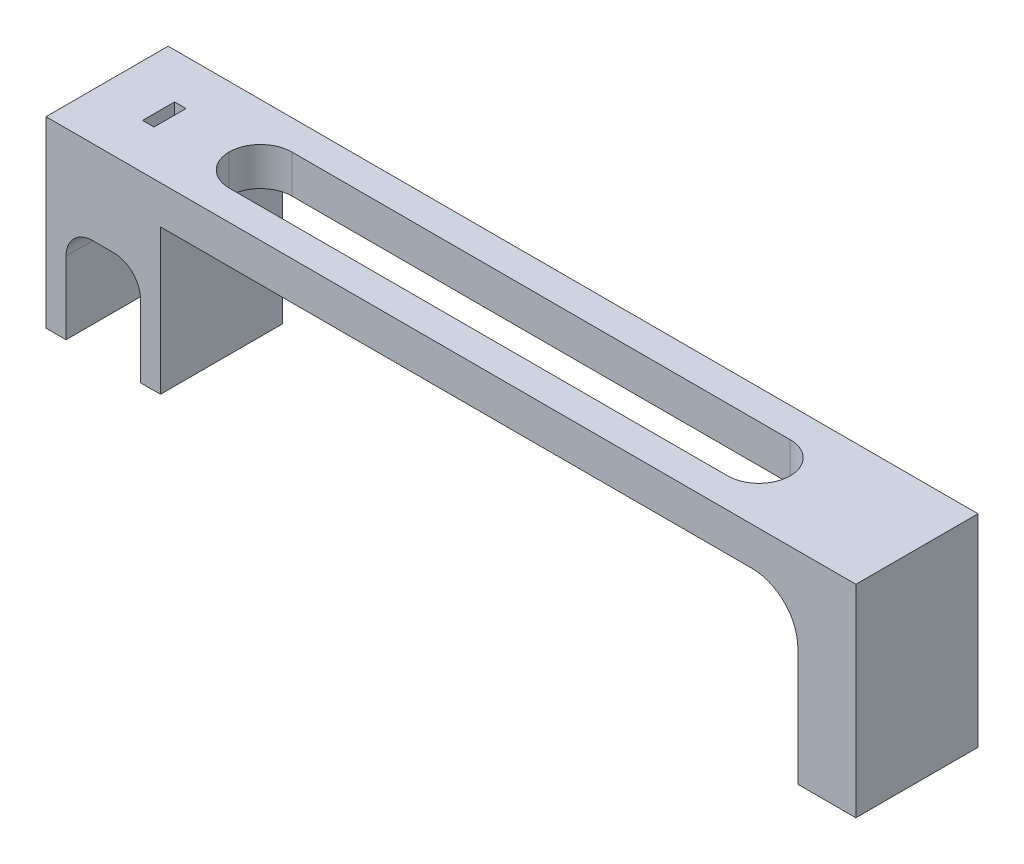
SolidWorks part; units mm, degrees
ref_plane "정면" through (0, 0, 0) normal (0, 0, 1) x (1, 0, 0)
ref_plane "윗면" through (0, 0, 0) normal (0, 1, 0) x (1, 0, 0)
ref_plane "우측면" through (0, 0, 0) normal (1, 0, 0) x (0, 0, -1)
sketch "스케치1" plane through (0, 0, 0) normal (0, 0, 1) x (1, 0, 0)
  line L0 (-96, 0) -> (0, 0)
  line L1 (0, 0) -> (0, -21.5)
  line L2 (0, -21.5) -> (7.6, -21.5)
  line L3 (7.6, -21.5) -> (7.6, 5)
  line L4 (7.6, 5) -> (-96, 5)
  line L5 (-96, 5) -> (-96, 0)
  dimension "D1" = 5
  dimension "D2" = 96
  dimension "D3" = 7.6
  dimension "D4" = 21.5
extrude "보스-돌출1" add sketch "스케치1" along normal blind 16
sketch "스케치4" plane through (0, 0, 0) normal (0, -1, 0) x (1, 0, 0)
  line L0 (-96, 8) -> (-7.1358, 8) construction
  line L1 (-96, 16) -> (-96, 0) construction
  line L2 (0, 16) -> (0, 0) construction
  line L3 (-91.75, 5.9) -> (-90.25, 5.9)
  line L4 (-91.75, 5.9) -> (-91.75, 10.1)
  line L5 (-91.75, 10.1) -> (-90.25, 10.1)
  line L6 (-90.25, 5.9) -> (-90.25, 10.1)
  line L7 (-91.75, 5.9) -> (-90.25, 10.1) construction
  line L8 (-91.75, 10.1) -> (-90.25, 5.9) construction
  line L9 (-9, 3.9) -> (-82.5, 3.9)
  line L10 (-9, 3.9) -> (-9, 12.1)
  line L11 (-9, 12.1) -> (-82.5, 12.1)
  line L12 (-82.5, 3.9) -> (-82.5, 12.1)
  line L13 (-9, 3.9) -> (-82.5, 12.1) construction
  line L14 (-9, 12.1) -> (-82.5, 3.9) construction
  point P4 (-91, 8)
  point P9 (-45.75, 8)
  dimension "D1" = 1.5
  dimension "D2" = 4.25
  dimension "D3" = 7.75
  dimension "D4" = 9
  dimension "D5" = 8.2
  dimension "D6" = 4.2
extrude "컷-돌출1" cut sketch "스케치4" against normal blind 10
fillet "필렛1" radius 4.1 4 edges at (-82.5, 2.5, 3.9) (-82.5, 2.5, 12.1) (-9, 2.5, 3.9) (-9, 2.5, 12.1)
sketch "스케치6" plane through (0, 5, 0) normal (0, 1, 0) x (1, 0, 0)
  line L0 (7.6, -16) -> (-96, -16) construction
  line L1 (-96, 0) -> (-86, 0)
  line L2 (-96, 0) -> (-96, -16)
  line L3 (-96, -16) -> (-86, -16)
  line L4 (-86, 0) -> (-86, -16)
  line L6 (-90.25, -5.9) -> (-90.25, -10.1) construction
  line M5 (-91.75, -5.9) -> (-90.25, -5.9)
  line M6 (-90.25, -5.9) -> (-90.25, -10.1)
  line M7 (-90.25, -10.1) -> (-91.75, -10.1)
  line M8 (-91.75, -10.1) -> (-91.75, -5.9)
  line M15 (7.6, 0) -> (-96, 0)
  line M16 (-96, 0) -> (-96, -16)
  line M17 (-96, -16) -> (7.6, -16)
  dimension "D1" = 4.25
extrude "보스-돌출4" add sketch "스케치6" against normal blind 11 contours L4 M15 M16 M17 M8 M5 M6 M7 region at (-91, 5, 0.1887)
sketch "스케치7" plane through (0, -21.5, 0) normal (0, -1, 0) x (1, 0, 0)
  line L0 (3.8, 16) -> (3.8, 0) construction
  line L1 (0, 16) -> (7.6, 16) construction
  line L2 (0, 0) -> (7.6, 0) construction
  line L3 (0, 8) -> (7.6, 8) construction
  line L4 (0, 16) -> (0, 0) construction
  line L5 (7.6, 16) -> (7.6, 0) construction
  line L7 (0, 16) -> (7.6, 16)
  line L8 (0, 16) -> (0, 0)
  line L9 (0, 0) -> (7.6, 0)
  line L10 (7.6, 16) -> (7.6, 0)
  line L11 (7.6, 11.75) -> (0, 11.75)
  line L12 (7.6, 11.75) -> (7.6, 4.25)
  line L13 (7.6, 4.25) -> (0, 4.25)
  line L14 (0, 11.75) -> (0, 4.25)
  line L15 (7.6, 11.75) -> (0, 4.25) construction
  line L16 (7.6, 4.25) -> (0, 11.75) construction
  line L17 (7.6, 16) -> (0, 16)
  line L18 (7.6, 16) -> (7.6, 0)
  line L19 (7.6, 0) -> (0, 0)
  line L20 (0, 16) -> (0, 0)
  line L21 (7.6, 16) -> (0, 0) construction
  line L22 (7.6, 0) -> (0, 16) construction
  point P12 (3.8, 8)
  point P23 (3.8, 8)
  dimension "D1" = 7.5
sketch "스케치10" plane through (0, -6, 0) normal (0, -1, 0) x (1, 0, 0)
  line L0 (-91, 10.1) -> (-91, 5.9) construction
  line L1 (-90.25, 10.1) -> (-91.75, 10.1) construction
  line L2 (-91.75, 5.9) -> (-90.25, 5.9) construction
  line L3 (-91.75, 8) -> (-90.25, 8) construction
  line L4 (-91.75, 10.1) -> (-91.75, 5.9) construction
  line L5 (-90.25, 5.9) -> (-90.25, 10.1) construction
  line L7 (-95.875, 0) -> (-86.125, 0)
  line L8 (-95.875, 0) -> (-95.875, 16)
  line L9 (-95.875, 16) -> (-86.125, 16)
  line L10 (-86.125, 0) -> (-86.125, 16)
  line L11 (-95.875, 0) -> (-86.125, 16) construction
  line L12 (-95.875, 16) -> (-86.125, 0) construction
  line L13 (-98.5, 0) -> (-83.5, 0)
  line L14 (-98.5, 0) -> (-98.5, 16)
  line L15 (-98.5, 16) -> (-83.5, 16)
  line L16 (-83.5, 0) -> (-83.5, 16)
  line L17 (-98.5, 0) -> (-83.5, 16) construction
  line L18 (-98.5, 16) -> (-83.5, 0) construction
  point P12 (-91, 8)
  point P17 (-91, 8)
  line M6 (-86, 0) -> (-86, 16)
  line M7 (-86, 16) -> (-96, 16)
  line M8 (-96, 16) -> (-96, 0)
  line M9 (-96, 0) -> (-86, 0)
  dimension "D1" = 9.75
  dimension "D2" = 15
extrude "보스-돌출6" add sketch "스케치10" along normal blind 13 and the other way up to vertex (11 mm away) contours L8 M9 M7 M8 | L15 L14 L13 M8 | L10 M9 M6 M7 | L13 L16 L15 M6 region at (-95.9375, -6, 8) region at (-86.0625, -6, 8) region at (-97.25, -6, 8) region at (-84.75, -6, 8) other way up to point (7.6, 5, 16)
fillet "필렛2" radius 3.5 2 edges at (-86.125, -6, 8) (-95.875, -6, 8)
fillet "필렛3" radius 6 1 edges at (0, 0, 8)
